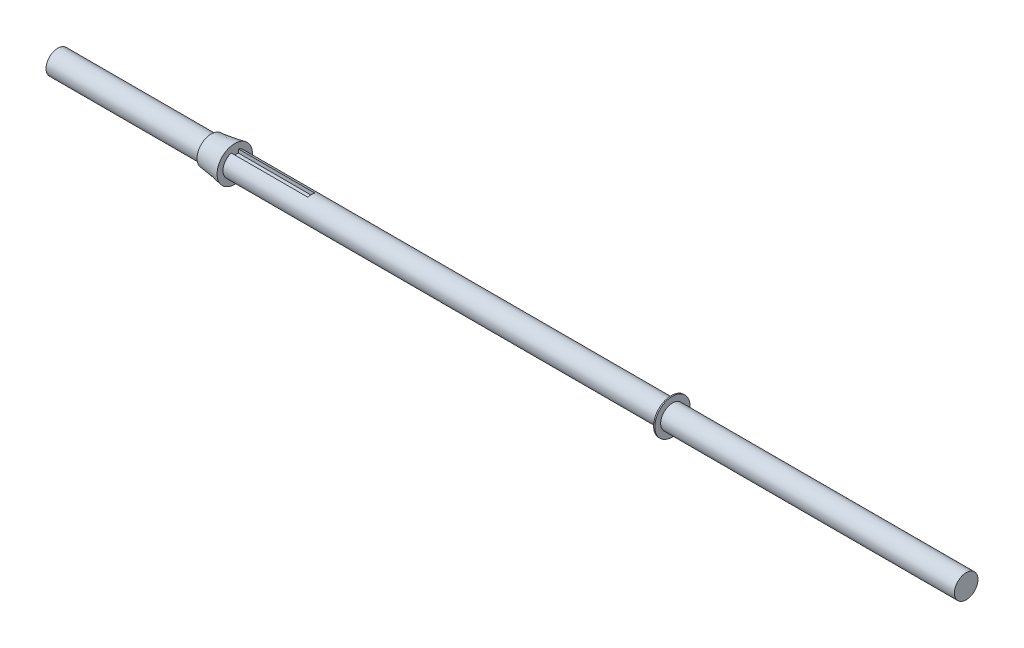
SolidWorks part; units mm, degrees
ref_plane "Front Plane" through (0, 0, 0) normal (0, 0, 1) x (1, 0, 0)
ref_plane "Top Plane" through (0, 0, 0) normal (0, 1, 0) x (1, 0, 0)
ref_plane "Right Plane" through (0, 0, 0) normal (1, 0, 0) x (0, 0, -1)
sketch "Sketch3" plane through (0, 0, 0) normal (1, 0, 0) x (0, 0, -1)
  circle A0 centre (0, 0) radius 10
extrude "Boss-Extrude1" add sketch "Sketch3" along normal blind 750
ref_plane "Plane1" through (130, 0, 0) normal (1, 0, 0) x (0, 0, -1)
sketch "Sketch4" plane through (130, 0, 0) normal (1, 0, 0) x (0, 0, -1)
  circle A0 centre (0, 0) radius 15
ref_plane "Plane2" through (110, 0, 0) normal (1, 0, 0) x (0, 0, -1)
sketch "Sketch5" plane through (110, 0, 0) normal (1, 0, 0) x (0, 0, -1)
  circle A0 centre (0, 0) radius 12
loft "Loft1" add profiles "Sketch4", "Sketch5" connector at (130, 13.4203, -6.7005) connector at (110, 7.7647, -9.1493)
ref_plane "Plane3" through (500, 0, 0) normal (1, 0, 0) x (0, 0, -1)
sketch "Sketch6" plane through (500, 0, 0) normal (1, 0, 0) x (0, 0, -1)
  circle A0 centre (0, 0) radius 15
extrude "Boss-Extrude2" add sketch "Sketch6" along normal blind 1
sketch "Sketch7" plane through (0, 0, 0) normal (-1, 0, 0) x (0, 0, 1)
  circle A0 centre (0, 0) radius 10
extrude "Boss-Extrude3" add sketch "Sketch7" along normal blind 20
ref_plane "Plane4" through (0, 12.5, 0) normal (0, 1, 0) x (1, 0, 0)
sketch "Sketch8" plane through (0, 12.5, 0) normal (0, 1, 0) x (1, 0, 0)
  line L0 (-20, -10) -> (-20, 10) construction
  line L1 (130, -3) -> (130, 3)
  line L2 (130, -3) -> (195, -3)
  line L4 (130, 0) -> (130, 3)
  line L5 (130, -10) -> (130, 10) construction
  line L6 (130, -15) -> (130, 15) construction
  line L7 (130, 3) -> (195, 3)
  line L8 (195, 3) -> (195, -3)
  point P8 (0, 0)
  point P14 (0, 0)
extrude "Cut-Extrude1" cut sketch "Sketch8" against normal blind 6 contours L1 L2 L8 L7
